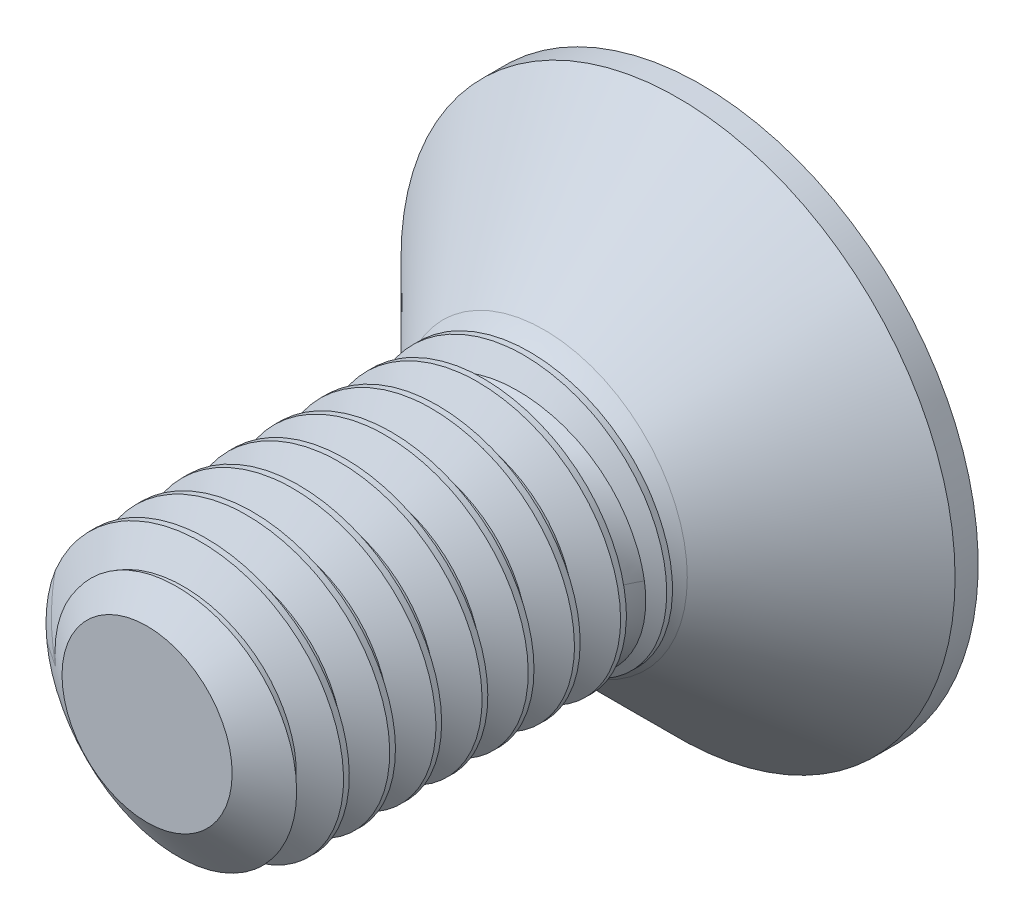
SolidWorks part; units mm, degrees
material "Alloy Steel"
ref_plane "Front Plane" through (0, 0, 0) normal (0, 0, 1) x (1, 0, 0)
ref_plane "Top Plane" through (0, 0, 0) normal (0, 1, 0) x (1, 0, 0)
ref_plane "Right Plane" through (0, 0, 0) normal (1, 0, 0) x (0, 0, -1)
sketch "Sketch1" plane through (0, 0, 0) normal (0, 0, 1) x (1, 0, 0)
  circle A0 centre (0, 0) radius 1.5
  dimension "OD" = 3
extrude "Extrude1" add sketch "Sketch1" against normal blind 6
sketch "Sketch2" plane through (0, 0, 0) normal (0, 0, 1) x (1, 0, 0)
  circle A0 centre (0, 0) radius 1.5 construction
  circle A1 centre (0, 0) radius 1.5
curve "Helix/Spiral1" pitch 0.5 height 6.5 radius 1.5 centre (0, 0, 0) axis (0, 0, -1) start towards (0, 1, 0) parameters "pitch"=0.5
sketch "Sketch3" plane through (0, 0, 0) normal (1, 0, 0) x (0, 0, -1)
  line L0 (-0.4375, 1.5) -> (-0.25, 1.1752)
  line L1 (-0.25, 1.1752) -> (-0.1875, 1.1752)
  line L2 (-0.1875, 1.1752) -> (0, 1.5)
  line L3 (-0.4375, 1.5) -> (0, 1.5)
  line L4 (-0.2188, 1.5) -> (-0.2188, 1.1752) construction
  line L5 (-0.3438, 1.3376) -> (-0.0937, 1.3376) construction
  line L6 (0, 1.5) -> (0, -1.5) construction
  dimension "D1" = 0.0625
  dimension "D2" = 0.25
  dimension "D3" = 60
sweep "Cut-Sweep1" cut profiles "Sketch3" path "Helix/Spiral1"
sketch "Sketch4" plane through (0, 0, 0) normal (1, 0, 0) x (0, 0, -1)
  line L0 (0.4053, 1.5) -> (0, 0.9212)
  line L1 (0, 0.9212) -> (0, 1.5)
  line L2 (0.4053, 1.5) -> (0, 1.5)
  line L3 (-0.4375, 1.5) -> (0, 1.5) construction
  line L4 (0, 0) -> (7.0209, 0) construction
  dimension "D1" = 55
  dimension "D2" = 0.254
revolve "Cut-Revolve1" cut sketch "Sketch4" angle 360 about L4
sketch "Sketch5" plane through (0, 0, 0) normal (1, 0, 0) x (0, 0, -1)
  line L0 (6, -1.1822) -> (6, 1.0703) construction
  line L1 (6, 1.55) -> (18.1906, 1.55)
  line L2 (6, 1.55) -> (6, 0)
  line L3 (6, 0) -> (18, 0)
  line L4 (18, 1.2198) -> (18, 0)
  line L5 (18.1906, 1.55) -> (18, 1.2198)
  line L6 (0, 0) -> (9.9695, 0) construction
  point P3 (18, 1.55)
  point P10 (18, 1.55)
  dimension "D1" = 0.3302
  dimension "Thread min" = 18
  dimension "D2" = 0.05
  dimension "D3" = 30
revolve "partially thread" [suppressed] add sketch "Sketch5" angle 360 about L6
sketch "Sketch6" plane through (0, 0, -6) normal (0, 0, -1) x (-1, 0, 0)
  circle A0 centre (0, 0) radius 3
  dimension "head dia" = 6
extrude "Extrude2" add sketch "Sketch6" against normal blind 1.7
sketch "Sketch10" plane through (0, 0, 0) normal (1, 0, 0) x (0, 0, -1)
  line L0 (5.75, -3) -> (4.3, -1.55)
  line L1 (4.3, -1.55) -> (4.3, -3)
  line L2 (5.75, -3) -> (4.3, -3)
  line L3 (0, 0) -> (4.3, 0) construction
  line L4 (4.3, 3) -> (4.3, -3) construction
  line L5 (5.75, 3) -> (4.3, 3) construction
  line L6 (4.3, 1.55) -> (4.3, 3) construction
  line L7 (5.75, 3) -> (4.3, 1.55) construction
  line L8 (4.3, 3) -> (4.3, -3) construction
  line L9 (4.3, 1.55) -> (4.3, -1.55) construction
  dimension "D1" = 45
  dimension "D2" = 0.05
revolve "Cut-Revolve2" cut sketch "Sketch10" angle 360 about L3
sketch "Sketch11" plane through (0, 0, 0) normal (1, 0, 0) x (0, 0, -1)
  line L0 (-0.25, 1.1752) -> (-0.1875, 1.1752) construction
  line L1 (5.75, 3) -> (4.3, 1.55) construction
  line L2 (3.3953, 1.1752) -> (3.3953, 0)
  line L3 (3.3953, 0) -> (4.3, 0)
  line L4 (4.3, 1.55) -> (4.3, 0)
  line L5 (0, 0) -> (4.3, 0) construction
  arc A0 (4.3, 1.55) -> (3.3953, 1.1752) centre (3.3953, 2.4547) cw
revolve "Revolve1" add sketch "Sketch11" angle 360 about L3
sketch "Sketch7" plane through (0, 0, -6) normal (0, 0, 1) x (1, 0, 0)
  line L1 (0, 1.1547) -> (-1, 0.5774)
  line L2 (-1, 0.5774) -> (-1, -0.5774)
  line L3 (-1, -0.5774) -> (0, -1.1547)
  line L4 (0, -1.1547) -> (1, -0.5774)
  line L5 (1, -0.5774) -> (1, 0.5774)
  line L6 (1, 0.5774) -> (0, 1.1547)
  circle A0 centre (0, 0) radius 1 construction
  dimension "hex dia" = 2
extrude "Cut-Extrude1" cut sketch "Sketch7" along normal blind 1.5
sketch "Sketch8" plane through (0, 0, -6) normal (0, 0, 1) x (1, 0, 0)
  circle A0 centre (0, 0) radius 1.1547
extrude "Cut-Extrude2" cut sketch "Sketch8" along normal through all draft 45
sketch "Sketch9" plane through (0, 0, 0) normal (1, 0, 0) x (0, 0, -1)
  line L0 (0, 1.5) -> (0, -1.5) construction
  line L1 (2.75, 1.5) -> (2.75, -1.5) construction
  line L2 (4.3, 1.5) -> (4.3, -1.5) construction
  line L3 (4.3, -1.55) -> (4.3, -3) construction
  dimension "D1" = 2.75
equation "\"D3@Helix/Spiral1\" = \"screw length@Extrude1\"+\"pitch@Helix/Spiral1\""
equation "\"D1@Sketch3\" = \"pitch@Helix/Spiral1\"*.125"
equation "\"D2@Sketch3\" = \"pitch@Helix/Spiral1\"*.5"
equation "\"D1@Cut-Extrude1\" = \"hex dia@Sketch7\"*.75"
equation "\"D1@Sketch9\" = \"pitch@Helix/Spiral1\"*5.5"
equation "\"D2@Sketch10\" = \"D2@Sketch5\""
